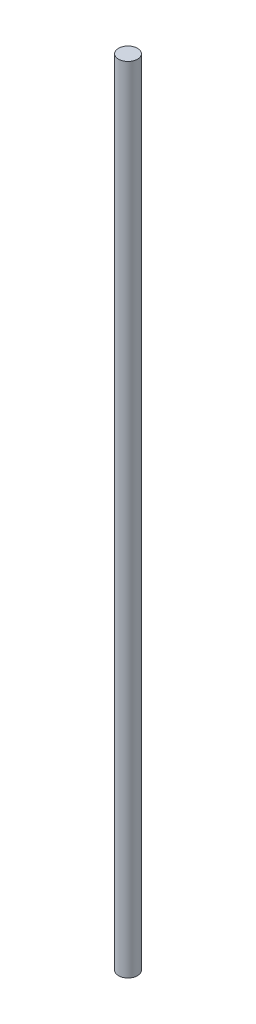
SolidWorks part; units mm, degrees
ref_plane "Front Plane" through (0, 0, 0) normal (0, 0, 1) x (1, 0, 0)
ref_plane "Top Plane" through (0, 0, 0) normal (0, 1, 0) x (1, 0, 0)
ref_plane "Right Plane" through (0, 0, 0) normal (1, 0, 0) x (0, 0, -1)
sketch "Sketch1" plane through (0, 0, 0) normal (0, 1, 0) x (1, 0, 0)
  circle A0 centre (0, 0) radius 4
  dimension "D1" = 8
extrude "Boss-Extrude1" add sketch "Sketch1" along normal blind 335
